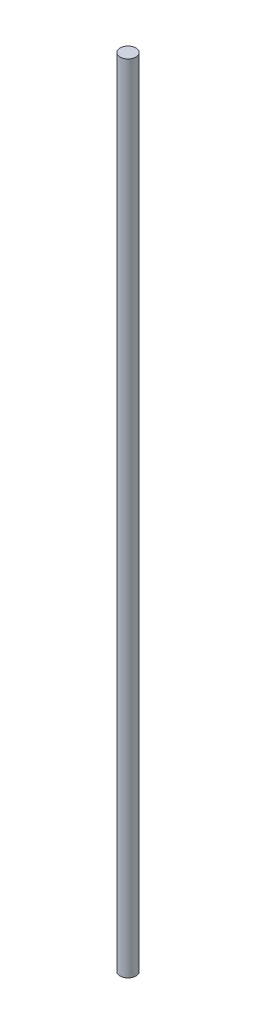
SolidWorks part; units mm, degrees
ref_plane "Front" through (0, 0, 0) normal (0, 0, 1) x (1, 0, 0)
ref_plane "Top" through (0, 0, 0) normal (0, 1, 0) x (1, 0, 0)
ref_plane "Right" through (0, 0, 0) normal (1, 0, 0) x (0, 0, -1)
sketch "Sketch1" plane through (0, 0, 0) normal (0, 1, 0) x (1, 0, 0)
  circle A0 centre (0, 0) radius 4
  dimension "D1" = 8
extrude "Boss-Extrude1" add sketch "Sketch1" along normal mid plane 400
